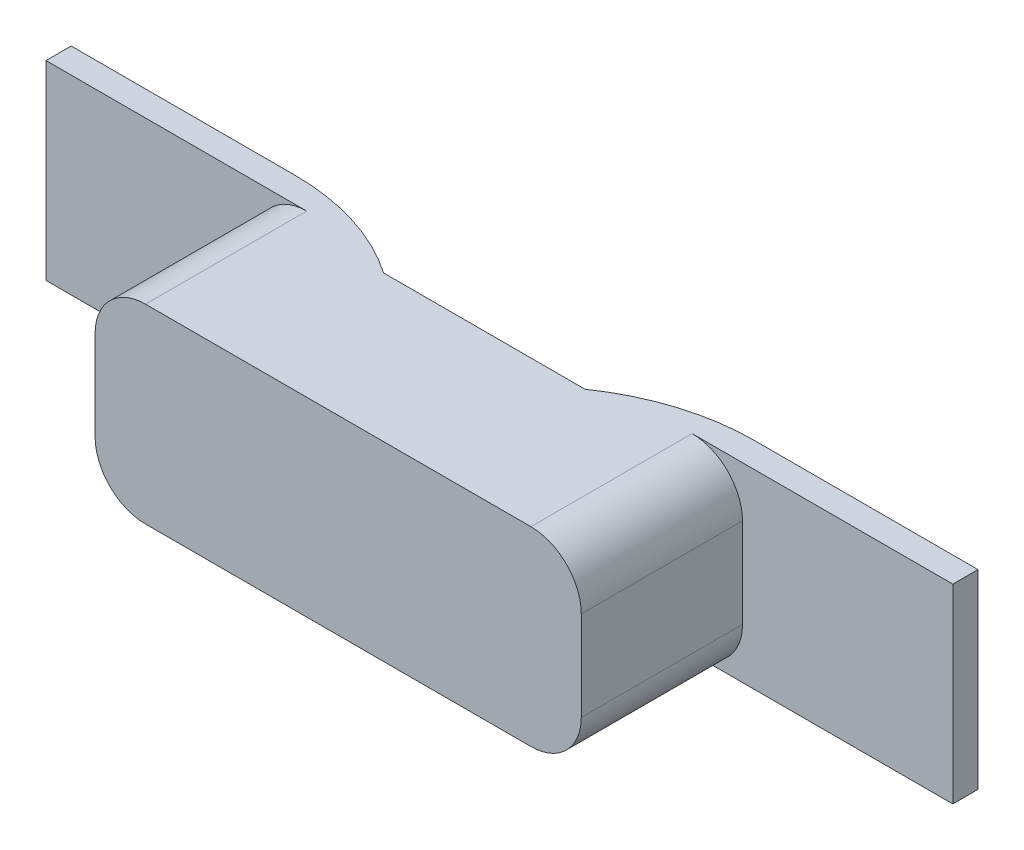
SolidWorks part; units mm, degrees
ref_plane "Спереди" through (0, 0, 0) normal (0, 0, 1) x (1, 0, 0)
ref_plane "Сверху" through (0, 0, 0) normal (0, 1, 0) x (1, 0, 0)
ref_plane "Справа" through (0, 0, 0) normal (1, 0, 0) x (0, 0, -1)
sketch "Sketch1" plane through (0, 0, 0) normal (0, 0, 1) x (1, 0, 0)
  line L1 (-9, -1.89) -> (9, -1.89)
  line L2 (-9, -1.89) -> (-9, 1.89)
  line L3 (-9, 1.89) -> (9, 1.89)
  line L4 (9, -1.89) -> (9, 1.89)
  line L5 (-9, -1.89) -> (9, 1.89) construction
  line L6 (-9, 1.89) -> (9, -1.89) construction
  point P0 (0, 0)
  dimension "D1" = 18
  dimension "D2" = 3.78
extrude "Boss-Extrude1" add sketch "Sketch1" along normal blind 0.5
sketch "Sketch3" plane through (0, 0, 0.5) normal (0, 0, 1) x (1, 0, 0)
  line L0 (9, 1.89) -> (-9, 1.89) construction
  line L1 (-3.825, -1.89) -> (3.825, -1.89)
  line L2 (-4.825, -0.89) -> (-4.825, 0.89)
  line L3 (-3.825, 1.89) -> (3.825, 1.89)
  line L4 (4.825, -0.89) -> (4.825, 0.89)
  line L5 (-4.825, -1.89) -> (4.825, 1.89) construction
  line L6 (-4.825, 1.89) -> (4.825, -1.89) construction
  arc A0 (3.825, -1.89) -> (4.825, -0.89) centre (3.825, -0.89) ccw
  arc A1 (-3.825, -1.89) -> (-4.825, -0.89) centre (-3.825, -0.89) cw
  arc A2 (3.825, 1.89) -> (4.825, 0.89) centre (3.825, 0.89) cw
  arc A3 (-4.825, 0.89) -> (-3.825, 1.89) centre (-3.825, 0.89) cw
  point P0 (0, 0)
  dimension "D2" = 1
  dimension "D1" = 9.65
extrude "Boss-Extrude2" add sketch "Sketch3" along normal blind 3.2
sketch "Sketch4" plane through (0, 0, 0) normal (0, 0, -1) x (-1, 0, 0)
  line L0 (-9, 1.89) -> (9, 1.89) construction
  line L1 (-2, -1.89) -> (2, -1.89)
  line L2 (-2, -1.89) -> (-2, 1.89)
  line L3 (-2, 1.89) -> (2, 1.89)
  line L4 (2, -1.89) -> (2, 1.89)
  line L5 (-2, -1.89) -> (2, 1.89) construction
  line L6 (-2, 1.89) -> (2, -1.89) construction
  point P0 (0, 0)
  dimension "D1" = 4
extrude "Cut-Extrude1" cut sketch "Sketch4" against normal blind 0.8
fillet "Fillet1" radius 4.5 2 edges at (-2, 0, 0) (2, 0, 0)
